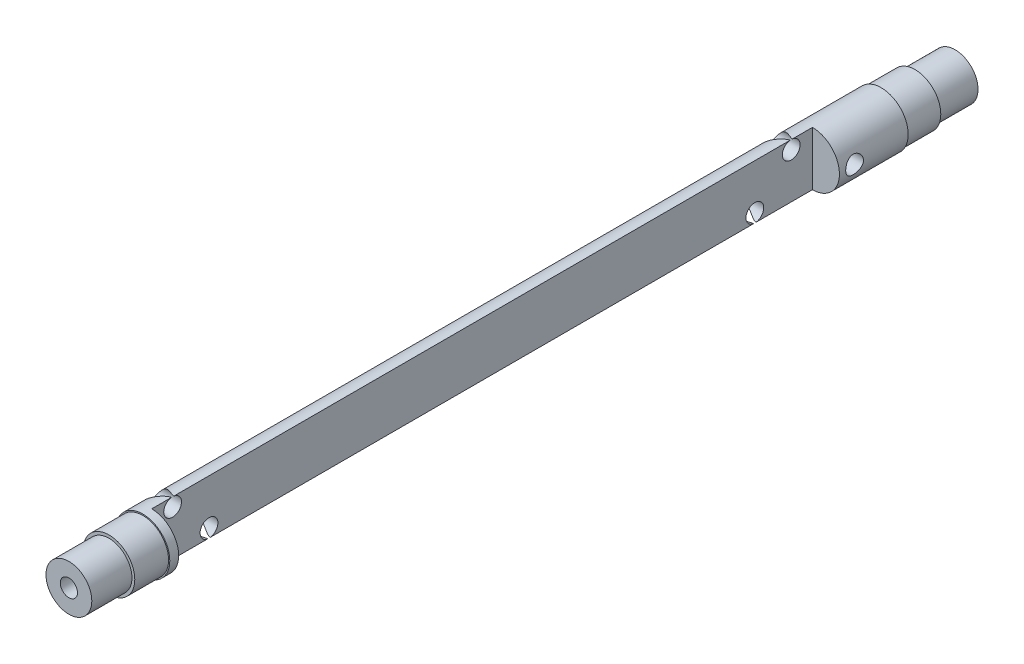
SolidWorks part; units mm, degrees
ref_plane "Front" through (0, 0, 0) normal (0, 0, 1) x (1, 0, 0)
ref_plane "Top" through (0, 0, 0) normal (0, 1, 0) x (1, 0, 0)
ref_plane "Right" through (0, 0, 0) normal (1, 0, 0) x (0, 0, -1)
sketch "Sketch1" plane through (0, 0, 0) normal (0, 0, 1) x (1, 0, 0)
  circle A0 centre (0, 0) radius 4.71
extrude "Extrude1" add sketch "Sketch1" along normal blind 128.85
sketch "Sketch3" plane through (0, 0, 128.85) normal (0, 0, 1) x (1, 0, 0)
  circle A0 centre (0, 0) radius 4.5
extrude "Extrude3" add sketch "Sketch3" along normal blind 5.9
sketch "Sketch4" plane through (0, 0, 134.75) normal (0, 0, 1) x (1, 0, 0)
  circle A0 centre (0, 0) radius 4
extrude "Extrude4" add sketch "Sketch4" along normal blind 7
sketch "Sketch5" plane through (0, 0, 0) normal (0, 0, -1) x (-1, 0, 0)
  circle A0 centre (0, 0) radius 4.5
extrude "Extrude5" add sketch "Sketch5" along normal blind 5.9
sketch "Sketch6" plane through (0, 0, -5.9) normal (0, 0, -1) x (-1, 0, 0)
  circle A0 centre (0, 0) radius 4
extrude "Extrude6" add sketch "Sketch6" along normal blind 7
sketch "Sketch7" plane through (0, 0, 0) normal (1, 0, 0) x (0, 0, -1)
  line L0 (-128.85, -4.71) -> (0, -4.71) construction
  line L1 (-127.3, 4.71) -> (-12, 4.71)
  line L2 (-127.3, 4.71) -> (-127.3, -4.71)
  line L3 (-127.3, -4.71) -> (-12, -4.71)
  line L4 (-12, 4.71) -> (-12, -4.71)
extrude "Cut-Extrude2" cut sketch "Sketch7" along normal through all
sketch "Sketch8" plane through (0, 0, 0) normal (1, 0, 0) x (0, 0, -1)
  circle A0 centre (-15.7, 3.175) radius 1.55
  circle A1 centre (-22.05, -3.175) radius 1.55
  circle A2 centre (-123.65, 3.175) radius 1.55
  circle A3 centre (-117.3, -3.175) radius 1.55
extrude "Cut-Extrude3" cut sketch "Sketch8" against normal through all
sketch "Sketch9" plane through (0, 0, 0) normal (1, 0, 0) x (0, 0, -1)
  line L0 (-128.85, 0) -> (0, 0) construction
  circle A0 centre (-9.35, 0) radius 1.55
extrude "Cut-Extrude4" cut sketch "Sketch9" against normal through all and the other way through all
sketch "Sketch10" plane through (0, 0, 141.75) normal (0, 0, 1) x (1, 0, 0)
  circle A0 centre (0, 0) radius 1.5
extrude "Cut-Extrude5" cut sketch "Sketch10" against normal blind 7
sketch "Sketch11" plane through (0, 0, -12.9) normal (0, 0, -1) x (-1, 0, 0)
  circle A0 centre (0, 0) radius 1.5
extrude "Cut-Extrude6" cut sketch "Sketch11" against normal blind 7
